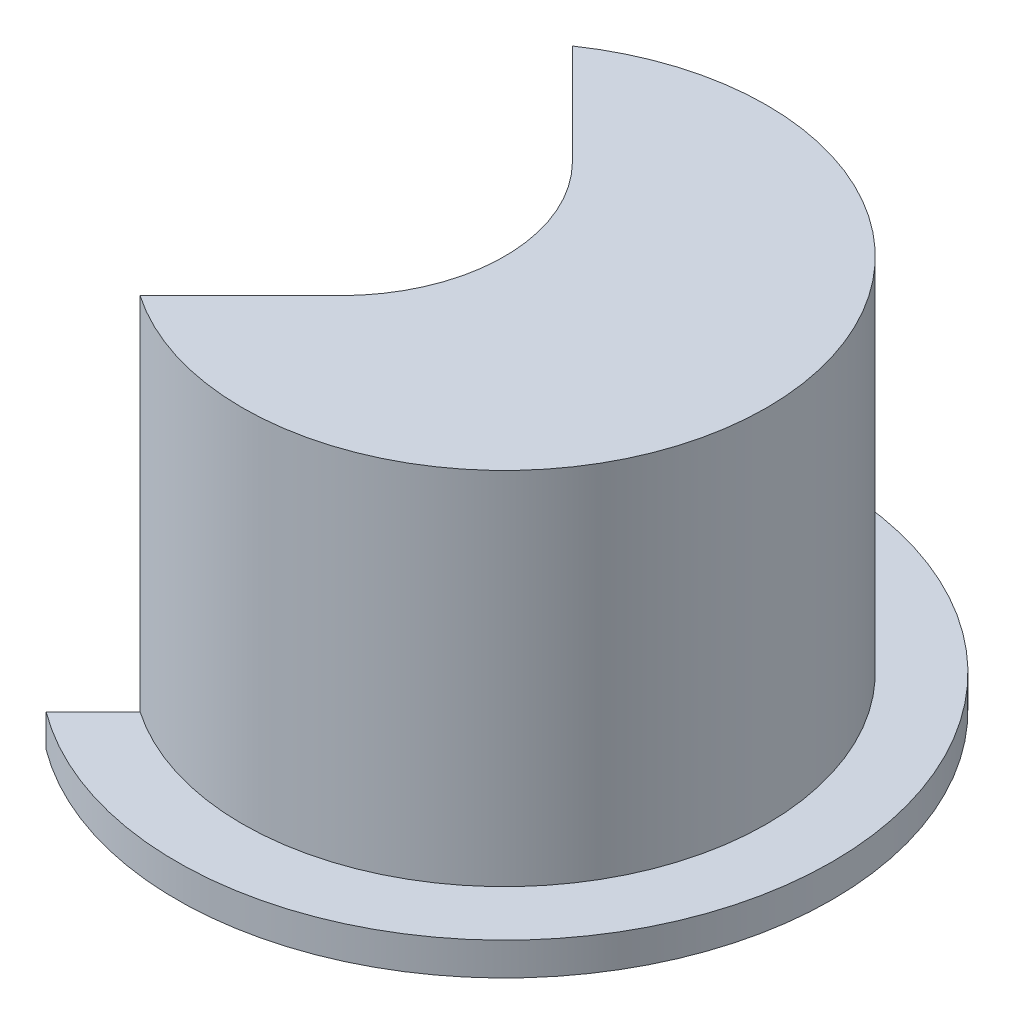
SolidWorks part; units mm, degrees
ref_plane "Front" through (0, 0, 0) normal (0, 0, 1) x (1, 0, 0)
ref_plane "Top" through (0, 0, 0) normal (0, 1, 0) x (1, 0, 0)
ref_plane "Right" through (0, 0, 0) normal (1, 0, 0) x (0, 0, -1)
other "Configuration Table"
sketch "Sketch1" plane through (0, 0, 0) normal (0, 1, 0) x (1, 0, 0)
  circle A0 centre (0, 0) radius 5
  circle A1 centre (0, 0) radius 4
  dimension "D1" = 10
  dimension "D2" = 8
extrude "Boss-Extrude1" add sketch "Sketch1" along normal blind 0.5
extrude "Boss-Extrude2" add sketch "Sketch1<3>" along normal blind 6 contours A1 region at (0, 0, 0)
sketch "Sketch1<3>" plane through (0, 0, 0) normal (0, 1, 0) x (1, 0, 0) same geometry as "Sketch1"
sketch "Sketch2" plane through (0, 0, 0) normal (0, 1, 0) x (1, 0, 0)
  line L0 (-0.7322, 1.7678) -> (-2.9796, 4.0152)
  line L1 (-0.7322, -1.7678) -> (-2.9796, -4.0152)
  line L2 (-7.1839, 0) -> (8.2942, 0) construction
  arc A0 (-0.7322, -1.7678) -> (-0.7322, 1.7678) centre (-2.5, 0) ccw
  circle A1 centre (0, 0) radius 5 construction
  arc A2 (-2.9796, 4.0152) -> (-2.9796, -4.0152) centre (0, 0) ccw
  dimension "D1" = 5
  dimension "45" = 45
extrude "Cut-Extrude2" cut sketch "Sketch2" along normal through all contours L2 A2 L1 A0 | A0 L0 A2 L1 region at (-2.6772, 0, 1.4777)
